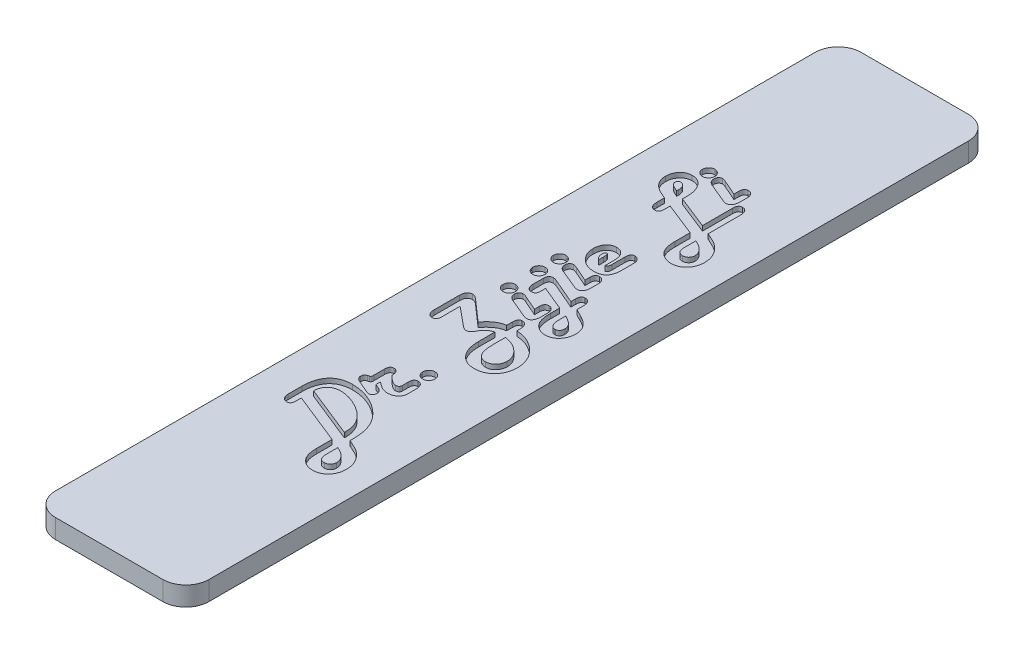
SolidWorks part; units mm, degrees
ref_plane "Front Plane" through (0, 0, 0) normal (0, 0, 1) x (1, 0, 0)
ref_plane "Top Plane" through (0, 0, 0) normal (0, 1, 0) x (1, 0, 0)
ref_plane "Right Plane" through (0, 0, 0) normal (1, 0, 0) x (0, 0, -1)
sketch "Sketch1" plane through (0, 0, 0) normal (0, 0, 1) x (1, 0, 0)
  line L0 (0, 1.5875) -> (0, -1.5875)
  line L1 (-12.7, 0) -> (12.7, 0) construction
  point P6 (0, 0)
  dimension "Width" = 25.4
  dimension "Thk" = 3.175
sketch "Sketch2" plane through (0, 0, 0) normal (1, 0, 0) x (0, 0, -1)
  line L0 (66.675, 0) -> (-66.675, 0)
  point P4 (0, 0)
  dimension "Length" = 133.35
sketch "Sketch3" plane through (0, 0, 0) normal (0, 0, 1) x (1, 0, 0)
  line L1 (12.7, 1.5875) -> (-12.7, 1.5875)
  line L2 (12.7, 1.5875) -> (12.7, -1.5875)
  line L3 (12.7, -1.5875) -> (-12.7, -1.5875)
  line L4 (-12.7, 1.5875) -> (-12.7, -1.5875)
  line L5 (12.7, 1.5875) -> (-12.7, -1.5875) construction
  line L6 (12.7, -1.5875) -> (-12.7, 1.5875) construction
  point P0 (0, 0)
extrude "Boss-Extrude1" add sketch "Sketch3" along normal up to vertex (66.675 mm away) and the other way up to vertex (66.675 mm away) up to point (0, 0, 66.675) other way up to point (0, 0, -66.675)
sketch "Sketch5" plane through (0, 1.5875, 0) normal (0, 1, 0) x (1, 0, 0)
  line L0 (-9.398, 66.929) -> (9.652, 66.929) construction
  line L1 (12.954, 63.627) -> (12.954, -63.373) construction
  line L2 (9.652, -66.675) -> (-9.398, -66.675) construction
  line L3 (-12.7, -63.373) -> (-12.7, 63.627) construction
  line L12 (12.7, -66.675) -> (12.7, 66.675)
  line L13 (12.7, 66.675) -> (-12.7, 66.675)
  line L14 (-12.7, 66.675) -> (-12.7, -66.675)
  line L15 (-12.7, -66.675) -> (12.7, -66.675)
  line L16 (12.7, -62.865) -> (12.7, 62.865)
  line L17 (8.89, 66.675) -> (-8.89, 66.675)
  line L18 (-12.7, 62.865) -> (-12.7, -62.865)
  line L19 (-8.89, -66.675) -> (8.89, -66.675)
  arc A0 (9.652, -66.675) -> (12.954, -63.373) centre (9.652, -63.373) ccw construction
  arc A1 (9.652, -66.675) -> (12.954, -63.373) centre (9.652, -63.373) ccw construction
  arc A2 (-12.7, -63.373) -> (-9.398, -66.675) centre (-9.398, -63.373) ccw construction
  arc A3 (-12.7, -63.373) -> (-9.398, -66.675) centre (-9.398, -63.373) ccw construction
  arc A4 (12.954, 63.627) -> (9.652, 66.929) centre (9.652, 63.627) ccw construction
  arc A5 (12.954, 63.627) -> (9.652, 66.929) centre (9.652, 63.627) ccw construction
  arc A6 (-9.398, 66.929) -> (-12.7, 63.627) centre (-9.398, 63.627) ccw construction
  arc A7 (-9.398, 66.929) -> (-12.7, 63.627) centre (-9.398, 63.627) ccw construction
  arc A8 (12.7, 62.865) -> (8.89, 66.675) centre (8.89, 62.865) ccw
  arc A9 (-8.89, 66.675) -> (-12.7, 62.865) centre (-8.89, 62.865) ccw
  arc A10 (12.7, -62.865) -> (8.89, -66.675) centre (8.89, -62.865) cw
  arc A11 (-8.89, -66.675) -> (-12.7, -62.865) centre (-8.89, -62.865) cw
  dimension "D2" = 3.81
  dimension "D1" = 0
extrude "Cut-Extrude2" cut sketch "Sketch5" against normal through all flip side to cut
sketch "Sketch4" plane through (0, 1.5875, 0) normal (0, 1, 0) x (1, 0, 0)
  line L0 (0, 0) -> (2.54, 0) construction
  line L1 (2.54, -66.675) -> (2.54, 66.675) construction
  line L2 (8.89, 66.675) -> (-8.89, 66.675) construction
  text T0 "Dr. Zijie Li" font "Harlow Solid Italic" height 10
  point P8 (2.54, 0)
  dimension "D1" = 2.54
extrude "Cut-Extrude1" cut sketch "Sketch4" against normal blind 0.7937
